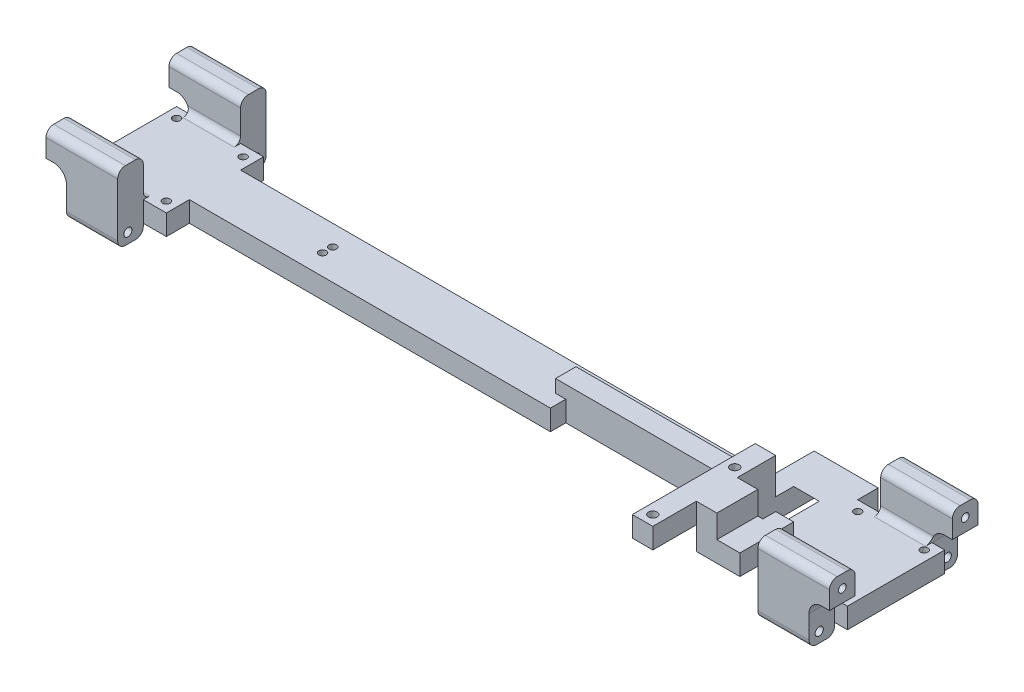
SolidWorks part; units mm, degrees
ref_plane "Front" through (0, 0, 0) normal (0, 0, 1) x (1, 0, 0)
ref_plane "Top" through (0, 0, 0) normal (0, 1, 0) x (1, 0, 0)
ref_plane "Right" through (0, 0, 0) normal (1, 0, 0) x (0, 0, -1)
sketch "Sketch1" plane through (0, 0, 0) normal (0, 1, 0) x (1, 0, 0)
  line L1 (0, 0) -> (300, 0)
  line L2 (0, 0) -> (0, -20)
  line L3 (0, -20) -> (300, -20)
  line L4 (300, 0) -> (300, -20)
  dimension "D1" = 20
  dimension "D2" = 300
extrude "Boss-Extrude1" add sketch "Sketch1" along normal blind 8
sketch "Sketch2" plane through (0, 0, 20) normal (0, 0, 1) x (1, 0, 0)
  line L0 (0, 8) -> (300, 8) construction
  line L1 (0, 0) -> (34, 0)
  line L2 (0, 0) -> (0, 8)
  line L3 (0, 8) -> (34, 8)
  line L4 (34, 0) -> (34, 8)
  line L5 (266, 8) -> (300, 8)
  line L6 (300, 0) -> (300, 8)
  line L7 (266, 0) -> (300, 0)
  line L8 (266, 0) -> (266, 8)
  dimension "D1" = 34
  dimension "D2" = 2
extrude "Boss-Extrude2" add sketch "Sketch2" along normal blind 9
sketch "Sketch3" plane through (0, 0, 0) normal (0, 0, -1) x (-1, 0, 0)
  line L0 (-300, 8) -> (0, 8) construction
  line L1 (0, 0) -> (-34, 0)
  line L2 (0, 0) -> (0, 8)
  line L3 (0, 8) -> (-34, 8)
  line L4 (-34, 0) -> (-34, 8)
  line L5 (-300, 0) -> (-300, 8)
  line L6 (-266, 8) -> (-300, 8)
  line L7 (-266, 0) -> (-266, 8)
  line L8 (-266, 0) -> (-300, 0)
  dimension "D1" = 34
  dimension "D2" = 2
extrude "Boss-Extrude3" add sketch "Sketch3" along normal blind 9
sketch "Sketch4" plane through (0, 8, 0) normal (0, 1, 0) x (1, 0, 0)
  line L0 (0, 9) -> (34, 9) construction
  line L1 (0, 9) -> (0, -29) construction
  circle A0 centre (4, 5) radius 1.45
  circle A1 centre (30, 5) radius 1.45
  circle A2 centre (30, -25) radius 1.45
  circle A3 centre (4, -25) radius 1.45
  circle A4 centre (296, -25) radius 1.45
  circle A5 centre (296, 5) radius 1.45
  circle A6 centre (270, -25) radius 1.45
  circle A7 centre (270, 5) radius 1.45
  dimension "D1" = 2.9
  dimension "D2" = 4
  dimension "D3" = 4
  dimension "D4" = 2
  dimension "D5" = 2
  dimension "D6" = 2
extrude "Cut-Extrude1" cut sketch "Sketch4" against normal through all
sketch "Sketch5" plane through (0, 0, 20) normal (0, 0, 1) x (1, 0, 0)
  line L0 (34, 8) -> (266, 8) construction
  line L1 (266, 0) -> (241, 0)
  line L2 (266, 0) -> (266, 8)
  line L3 (266, 8) -> (241, 8)
  line L4 (241, 0) -> (241, 8)
  dimension "D1" = 25
extrude "Boss-Extrude4" add sketch "Sketch5" along normal blind 17
sketch "Sketch6" plane through (0, 0, 0) normal (0, 0, -1) x (-1, 0, 0)
  line L0 (-266, 0) -> (-34, 0) construction
  line L1 (-266, 8) -> (-241, 8)
  line L2 (-266, 8) -> (-266, 0)
  line L3 (-266, 0) -> (-241, 0)
  line L4 (-241, 8) -> (-241, 0)
  dimension "D1" = 25
extrude "Boss-Extrude5" add sketch "Sketch6" along normal blind 17
sketch "Sketch12" plane through (0, 0, 37) normal (0, 0, 1) x (1, 0, 0)
  line L0 (241, 0) -> (266, 0) construction
  line L1 (241, 8) -> (249, 8)
  line L2 (241, 8) -> (241, 0)
  line L3 (241, 0) -> (249, 0)
  line L4 (249, 8) -> (249, 0)
  dimension "D1" = 8
extrude "Boss-Extrude7" add sketch "Sketch12" along normal blind 17
sketch "Sketch14" plane through (0, 0, 29) normal (0, 0, 1) x (1, 0, 0)
  line L0 (300, 8) -> (266, 8) construction
  line L1 (295, 8) -> (275, 8)
  line L2 (295, 8) -> (295, -4)
  line L3 (295, -4) -> (275, -4)
  line L4 (275, 8) -> (275, -4)
  line L7 (266, 8) -> (266, 0) construction
  dimension "D1" = 20
  dimension "D2" = 9
  dimension "D3" = 12
  dimension "D4" = 12
extrude "Boss-Extrude8" add sketch "Sketch14" along normal blind 10
sketch "Sketch15" plane through (295, 0, 0) normal (1, 0, 0) x (0, 0, -1)
  line L0 (-39, -4) -> (-39, 8) construction
  line L2 (-39, -4) -> (-29, -4) construction
  circle A0 centre (-35, 0) radius 1.6
  dimension "D1" = 3.2
  dimension "D2" = 4
  dimension "D3" = 4
extrude "Cut-Extrude7" cut sketch "Sketch15" against normal blind 20
sketch "Sketch16" plane through (0, 0, -9) normal (0, 0, -1) x (-1, 0, 0)
  line L0 (-266, 8) -> (-300, 8) construction
  line L1 (-295, 8) -> (-275, 8)
  line L2 (-295, 8) -> (-295, -4)
  line L3 (-295, -4) -> (-275, -4)
  line L4 (-275, 8) -> (-275, -4)
  line L6 (-266, 0) -> (-266, 8) construction
  dimension "D1" = 20
  dimension "D2" = 9
  dimension "D3" = 12
extrude "Boss-Extrude9" add sketch "Sketch16" along normal blind 10
sketch "Sketch17" plane through (295, 0, 0) normal (1, 0, 0) x (0, 0, -1)
  line L0 (19, -4) -> (9, -4) construction
  line L1 (19, 8) -> (19, -4) construction
  circle A0 centre (15, 0) radius 1.6
  dimension "D1" = 3.2
  dimension "D2" = 4
  dimension "D3" = 4
extrude "Cut-Extrude8" cut sketch "Sketch17" against normal blind 20
sketch "Sketch18" plane through (0, 0, -9) normal (0, 0, -1) x (-1, 0, 0)
  line L0 (0, 8) -> (-34, 8) construction
  line L1 (-25, 8) -> (-5, 8)
  line L2 (-25, 8) -> (-25, -4)
  line L3 (-25, -4) -> (-5, -4)
  line L4 (-5, 8) -> (-5, -4)
  line L6 (-34, 8) -> (-34, 0) construction
  dimension "D1" = 20
  dimension "D2" = 9
  dimension "D3" = 12
extrude "Boss-Extrude10" add sketch "Sketch18" along normal blind 10
sketch "Sketch19" plane through (5, 0, 0) normal (-1, 0, 0) x (0, 0, 1)
  line L0 (-19, -4) -> (-19, 8) construction
  line L2 (-19, -4) -> (-9, -4) construction
  circle A0 centre (-15, 0) radius 1.6
  dimension "D1" = 3.2
  dimension "D2" = 4
  dimension "D3" = 4
extrude "Cut-Extrude9" cut sketch "Sketch19" against normal blind 20
sketch "Sketch20" plane through (0, 0, 29) normal (0, 0, 1) x (1, 0, 0)
  line L0 (34, 8) -> (0, 8) construction
  line L1 (5, 8) -> (25, 8)
  line L2 (5, 8) -> (5, -4)
  line L3 (5, -4) -> (25, -4)
  line L4 (25, 8) -> (25, -4)
  line L6 (34, 0) -> (34, 8) construction
  dimension "D1" = 20
  dimension "D2" = 9
  dimension "D3" = 12
extrude "Boss-Extrude11" add sketch "Sketch20" along normal blind 10
sketch "Sketch21" plane through (5, 0, 0) normal (-1, 0, 0) x (0, 0, 1)
  line L0 (39, 8) -> (39, -4) construction
  line L1 (39, -4) -> (29, -4) construction
  circle A0 centre (35, 0) radius 1.6
  dimension "D1" = 3.2
  dimension "D2" = 4
  dimension "D3" = 4
extrude "Cut-Extrude10" cut sketch "Sketch21" against normal blind 20
sketch "Sketch22" plane through (0, 8, 0) normal (0, 1, 0) x (1, 0, 0)
  line L0 (241, 17) -> (241, 0) construction
  line L1 (259, 9) -> (249, 9)
  line L2 (259, 9) -> (259, -29)
  line L3 (259, -29) -> (249, -29)
  line L4 (249, 9) -> (249, -29)
  line L5 (241, 17) -> (266, 17) construction
  line L6 (266, -37) -> (249, -37) construction
  dimension "D1" = 8
  dimension "D2" = 10
  dimension "D3" = 8
  dimension "D4" = 8
extrude "Cut-Extrude11" cut sketch "Sketch22" against normal through all
sketch "Sketch23" plane through (0, 0, 0) normal (0, -1, 0) x (-1, 0, 0)
  line L0 (-259, -29) -> (-259, 9) construction
  line L1 (-259, -19) -> (-267, -19)
  line L2 (-259, -19) -> (-259, -1)
  line L3 (-259, -1) -> (-267, -1)
  line L4 (-267, -19) -> (-267, -1)
  line L5 (-249, -29) -> (-259, -29) construction
  dimension "D1" = 8
  dimension "D2" = 10
  dimension "D3" = 10
extrude "Cut-Extrude12" cut sketch "Sketch23" against normal blind 4
sketch "Sketch24" plane through (259, 0, 0) normal (-1, 0, 0) x (0, 0, 1)
  line L0 (-9, 0) -> (-9, 8)
  line L1 (-9, 8) -> (-1, 8)
  line L2 (29, 8) -> (-9, 8) construction
  line L3 (-1, 8) -> (-9, 0)
  line L4 (29, 0) -> (29, 8)
  line L5 (29, 8) -> (21, 8)
  line L6 (21, 8) -> (29, 0)
  dimension "D1" = 8
  dimension "D2" = 8
extrude "Boss-Extrude12" add sketch "Sketch24" along normal blind 10
sketch "Sketch25" plane through (267, 0, 0) normal (-1, 0, 0) x (0, 0, 1)
  line L0 (19, 0) -> (19, 4)
  line L1 (19, 4) -> (15, 4)
  line L2 (1, 4) -> (19, 4) construction
  line L3 (15, 4) -> (19, 0)
  line L4 (1, 4) -> (5, 4)
  line L5 (5, 4) -> (1, 0)
  line L6 (1, 0) -> (1, 4)
  dimension "D1" = 4
  dimension "D2" = 4
extrude "Boss-Extrude13" add sketch "Sketch25" along normal blind 8
sketch "Sketch26" plane through (0, 8, 0) normal (0, 1, 0) x (1, 0, 0)
  line L0 (249, 1) -> (249, -21) construction
  line L1 (241, -54) -> (249, -54)
  line L2 (241, -54) -> (241, -6)
  line L3 (241, -6) -> (249, -6)
  line L4 (249, -54) -> (249, -6)
  dimension "D1" = 48
extrude "Boss-Extrude14" add sketch "Sketch26" along normal blind 14
sketch "Sketch27" plane through (0, 8, 0) normal (0, 1, 0) x (1, 0, 0)
  line L0 (249, -21) -> (259, -21) construction
  line L1 (249, -37) -> (257, -37)
  line L2 (249, -37) -> (249, -21)
  line L3 (249, -21) -> (257, -21)
  line L4 (257, -37) -> (257, -21)
  dimension "D1" = 8
extrude "Boss-Extrude15" add sketch "Sketch27" along normal blind 14
sketch "Sketch28" plane through (0, 0, 0) normal (0, -1, 0) x (1, 0, 0)
  line L0 (249, -9) -> (249, 29) construction
  line L1 (241, 54) -> (249, 54)
  line L2 (241, 54) -> (241, 14)
  line L3 (241, 14) -> (249, 14)
  line L4 (249, 54) -> (249, 14)
  dimension "D1" = 40
extrude "Cut-Extrude13" cut sketch "Sketch28" against normal blind 14
sketch "Sketch30" plane through (257, 0, 0) normal (1, 0, 0) x (0, 0, -1)
  line L0 (-37, 22) -> (-21, 22) construction
  line L1 (-21, 22) -> (-37, 22)
  line L2 (-21, 22) -> (-21, 8)
  line L3 (-21, 8) -> (-37, 8)
  line L4 (-37, 22) -> (-37, 8)
extrude "Boss-Extrude16" add sketch "Sketch30" along normal blind 9
sketch "Sketch31" plane through (0, 0, 0) normal (0, -1, 0) x (-1, 0, 0)
  line L1 (-249, -37) -> (-266, -37)
  line L2 (-249, -37) -> (-249, -29)
  line L3 (-249, -29) -> (-266, -29)
  line L4 (-266, -37) -> (-266, -29)
extrude "Cut-Extrude14" cut sketch "Sketch31" against normal blind 5
sketch "Sketch32" plane through (266, 0, 0) normal (1, 0, 0) x (0, 0, -1)
  line L0 (-37, 5) -> (-37, 22) construction
  line L1 (-21, 22) -> (-37, 22)
  line L2 (-21, 22) -> (-21, 13)
  line L3 (-21, 13) -> (-37, 13)
  line L4 (-37, 22) -> (-37, 13)
  dimension "D1" = 9
extrude "Cut-Extrude15" cut sketch "Sketch32" against normal blind 9
sketch "Sketch33" plane through (249, 0, 0) normal (-1, 0, 0) x (0, 0, 1)
  line L0 (29, 5) -> (24, 5)
  line L1 (21, 8) -> (29, 0) construction
  line L2 (24, 5) -> (29, 0)
  line L3 (29, 0) -> (29, 5)
extrude "Cut-Extrude16" cut sketch "Sketch33" against normal blind 10
sketch "Sketch34" plane through (0, 0, 29) normal (0, 0, 1) x (1, 0, 0)
  line L1 (266, 5) -> (259, 5)
  line L2 (266, 5) -> (266, 0)
  line L3 (266, 0) -> (259, 0)
  line L4 (259, 5) -> (259, 0)
extrude "Cut-Extrude17" cut sketch "Sketch34" against normal blind 5
sketch "Sketch35" plane through (0, 0, 21) normal (0, 0, -1) x (-1, 0, 0)
  line L0 (-249, 8) -> (-259, 8) construction
  line L1 (-259, 8) -> (-266, 8)
  line L2 (-259, 8) -> (-259, 13)
  line L3 (-259, 13) -> (-266, 13)
  line L4 (-266, 8) -> (-266, 13)
  line L5 (-266, 8) -> (-259, 8) construction
  line L6 (-266, 8) -> (-266, 13) construction
extrude "Boss-Extrude17" add sketch "Sketch35" along normal blind 5
sketch "Sketch36" plane through (0, 22, 0) normal (0, 1, 0) x (1, 0, 0)
  line L0 (241, -54) -> (249, -54) construction
  line L1 (249, -54) -> (249, -37) construction
  circle A0 centre (245, -50) radius 1.7
  circle A1 centre (245, -18) radius 1.7
  dimension "D1" = 3.4
  dimension "D2" = 4
  dimension "D3" = 4
  dimension "D4" = 2
extrude "Cut-Extrude18" cut sketch "Sketch36" against normal through all
sketch "Sketch37" plane through (0, 8, 0) normal (0, 1, 0) x (1, 0, 0)
  line L0 (241, -6) -> (171, -6)
  line L1 (241, -6) -> (241, -14) construction
  line L2 (241, -6) -> (241, -14)
  line L3 (241, -14) -> (241, -20) construction
  line L4 (241, -14) -> (171, -14)
  line L5 (171, -14) -> (171, -6)
  dimension "D1" = 70
extrude "Boss-Extrude18" add sketch "Sketch37" along normal blind 5
sketch "Sketch39" plane through (0, 8, 0) normal (0, 1, 0) x (1, 0, 0)
  line L0 (34, -20) -> (241, -20) construction
  line L1 (241, -14) -> (175, -14)
  line L2 (241, -14) -> (241, -20)
  line L3 (241, -20) -> (175, -20)
  line L4 (175, -14) -> (175, -20)
  dimension "D1" = 66
extrude "Cut-Extrude19" cut sketch "Sketch39" against normal through all
sketch "Sketch40" plane through (0, 8, 0) normal (0, 1, 0) x (1, 0, 0)
  line L1 (5, 9) -> (25, 9)
  line L2 (5, 9) -> (5, 19)
  line L3 (5, 19) -> (25, 19)
  line L4 (25, 9) -> (25, 19)
extrude "Boss-Extrude19" add sketch "Sketch40" along normal blind 10
sketch "Sketch41" plane through (0, 18, 0) normal (0, 1, 0) x (1, 0, 0)
  line L0 (25, 19) -> (5, 19) construction
  line L1 (25, 19) -> (-3, 19)
  line L2 (25, 19) -> (25, 9)
  line L3 (25, 9) -> (-3, 9)
  line L4 (-3, 19) -> (-3, 9)
  line L5 (5, 9) -> (25, 9) construction
  line L6 (25, 9) -> (25, 19) construction
  line L7 (5, 19) -> (5, 9) construction
  dimension "D1" = 28
  dimension "D2" = 20
extrude "Boss-Extrude20" add sketch "Sketch41" along normal blind 5 and the other way blind 5
sketch "Sketch42" plane through (-3, 0, 0) normal (-1, 0, 0) x (0, 0, 1)
  line L0 (-19, 23) -> (-9, 23) construction
  line L1 (-9, 13) -> (-9, 23) construction
  circle A0 centre (-14, 18) radius 1.5
  dimension "D1" = 3
  dimension "D2" = 5
  dimension "D3" = 5
extrude "Cut-Extrude20" cut sketch "Sketch42" against normal blind 15
sketch "Sketch43" plane through (0, 8, 0) normal (0, 1, 0) x (1, 0, 0)
  line L1 (5, -39) -> (25, -39)
  line L2 (5, -39) -> (5, -29)
  line L3 (5, -29) -> (25, -29)
  line L4 (25, -39) -> (25, -29)
extrude "Boss-Extrude21" add sketch "Sketch43" along normal blind 10
sketch "Sketch44" plane through (0, 18, 0) normal (0, 1, 0) x (1, 0, 0)
  line L0 (25, -29) -> (5, -29) construction
  line L1 (-3, -29) -> (25, -29)
  line L2 (-3, -29) -> (-3, -39)
  line L3 (-3, -39) -> (25, -39)
  line L4 (25, -29) -> (25, -39)
  line L5 (5, -39) -> (25, -39) construction
  line L6 (25, -39) -> (25, -29) construction
  line L7 (5, -29) -> (5, -39) construction
  dimension "D1" = 28
  dimension "D2" = 20
extrude "Boss-Extrude22" add sketch "Sketch44" along normal blind 5 and the other way blind 5
sketch "Sketch45" plane through (-3, 0, 0) normal (-1, 0, 0) x (0, 0, 1)
  line L0 (29, 23) -> (39, 23) construction
  line L1 (39, 13) -> (39, 23) construction
  circle A0 centre (34, 18) radius 1.5
  dimension "D1" = 3
  dimension "D2" = 5
  dimension "D3" = 5
extrude "Cut-Extrude21" cut sketch "Sketch45" against normal blind 15
sketch "Sketch46" plane through (0, 8, 0) normal (0, 1, 0) x (1, 0, 0)
  line L1 (295, 9) -> (275, 9)
  line L2 (295, 9) -> (295, 19)
  line L3 (295, 19) -> (275, 19)
  line L4 (275, 9) -> (275, 19)
  line L5 (295, -39) -> (275, -39)
  line L6 (295, -39) -> (295, -29)
  line L7 (295, -29) -> (275, -29)
  line L8 (275, -39) -> (275, -29)
extrude "Boss-Extrude23" add sketch "Sketch46" along normal blind 10
sketch "Sketch47" plane through (0, 18, 0) normal (0, 1, 0) x (1, 0, 0)
  line L0 (295, 19) -> (275, 19) construction
  line L1 (275, 19) -> (303, 19)
  line L2 (275, 19) -> (275, 9)
  line L3 (275, 9) -> (303, 9)
  line L4 (303, 19) -> (303, 9)
  line L5 (275, 9) -> (295, 9) construction
  line L6 (295, -29) -> (275, -29) construction
  line L7 (275, -29) -> (303, -29)
  line L8 (275, -29) -> (275, -39)
  line L9 (275, -39) -> (303, -39)
  line L10 (303, -29) -> (303, -39)
  line L11 (275, -39) -> (295, -39) construction
  line L12 (275, 19) -> (275, 9) construction
  line L13 (295, 9) -> (295, 19) construction
  line L14 (275, -29) -> (275, -39) construction
  line L15 (295, -39) -> (295, -29) construction
  dimension "D1" = 28
  dimension "D2" = 20
  dimension "D3" = 28
  dimension "D4" = 20
extrude "Boss-Extrude24" add sketch "Sketch47" along normal blind 5 and the other way blind 5
sketch "Sketch48" plane through (303, 0, 0) normal (1, 0, 0) x (0, 0, -1)
  line L2 (-39, 13) -> (-39, 23) construction
  line L3 (19, 13) -> (19, 23) construction
  line L4 (9, 23) -> (19, 23) construction
  line L5 (-39, 23) -> (-29, 23) construction
  circle A0 centre (14, 18) radius 1.5
  circle A1 centre (-34, 18) radius 1.5
  dimension "D1" = 3
  dimension "D2" = 3
  dimension "D3" = 5
  dimension "D4" = 5
  dimension "D5" = 5
  dimension "D6" = 5
extrude "Cut-Extrude22" cut sketch "Sketch48" against normal blind 15
fillet "Fillet1" radius 5 4 edges at (295, 13, 34) (295, 13, -14) (5, 13, 34) (5, 13, -14)
fillet "Fillet2" radius 2.5 4 edges at (15, 8, -9) (15, 8, 29) (285, 8, 29) (285, 8, -9)
fillet "Fillet3" radius 3 8 edges at (285, -4, 39) (285, -4, 29) (285, -4, -19) (285, -4, -9) (15, -4, -19) (15, -4, -9) (15, -4, 29) (15, -4, 39)
fillet "Fillet4" radius 3 8 edges at (11, 23, -19) (11, 23, -9) (11, 23, 29) (11, 23, 39) (289, 23, -9) (289, 23, -19) (289, 23, 39) (289, 23, 29)
sketch "Sketch49" plane through (0, 8, 0) normal (0, 1, 0) x (1, 0, 0)
  line L0 (241, 0) -> (34, 0) construction
  line L1 (34, -20) -> (175, -20) construction
  line L2 (0, 9) -> (0, -29) construction
  circle A0 centre (78, -8) radius 1.45
  circle A1 centre (78, -12) radius 1.45
  point P4 (0, 0)
  point P7 (0, 0)
  dimension "D1" = 2.9
  dimension "D2" = 2.9
  dimension "D3" = 8
  dimension "D4" = 8
  dimension "D5" = 78
  dimension "D6" = 78
extrude "Cut-Extrude23" cut sketch "Sketch49" against normal through all
